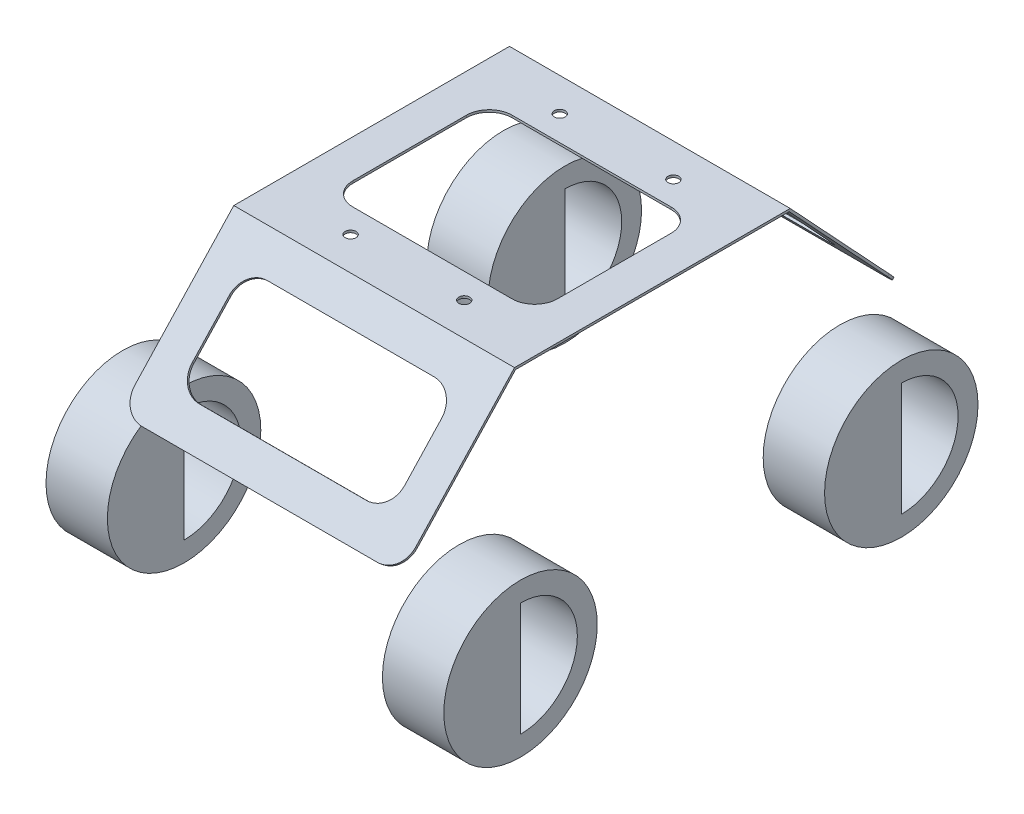
SolidWorks part; units mm, degrees
ref_plane "Plano frontal" through (0, 0, 0) normal (0, 0, 1) x (1, 0, 0)
ref_plane "Plano superior" through (0, 0, 0) normal (0, 1, 0) x (1, 0, 0)
ref_plane "Plano direito" through (0, 0, 0) normal (1, 0, 0) x (0, 0, -1)
sketch "Esboço1" plane through (0, 0, 0) normal (0, 1, 0) x (1, 0, 0)
  line L1 (-87.5, 117.5) -> (87.5, 117.5)
  line L2 (-87.5, 117.5) -> (-87.5, -117.5)
  line L3 (-87.5, -117.5) -> (87.5, -117.5)
  line L4 (87.5, 117.5) -> (87.5, -117.5)
  line L5 (-87.5, 117.5) -> (87.5, -117.5) construction
  line L6 (-87.5, -117.5) -> (87.5, 117.5) construction
  point P0 (0, 0)
  dimension "D1" = 175
  dimension "D2" = 235
extrude "Ressalto-extrusão1" add sketch "Esboço1" along normal blind 67.5
fillet "Filete1" radius 33.75 4 edges at (0, 0, -117.5) (0, 67.5, -117.5) (0, 0, 117.5) (0, 67.5, 117.5)
sketch "Esboço2" plane through (87.5, 0, 0) normal (1, 0, 0) x (0, 0, -1)
  line L0 (-83.75, 67.5) -> (83.75, 67.5)
  line L1 (83.75, 67.5) -> (83.75, 0) construction
  line L2 (83.75, 0) -> (-83.75, 0)
  line L3 (-83.75, 0) -> (-83.75, 67.5) construction
  circle A0 centre (-83.75, 33.75) radius 33.75 construction
  circle A1 centre (83.75, 33.75) radius 33.75 construction
  arc A2 (-83.75, 67.5) -> (-83.75, 0) centre (-83.75, 33.75) cw
  arc A3 (83.75, 67.5) -> (83.75, 0) centre (83.75, 33.75) ccw
extrude "Corte-extrusão1" cut sketch "Esboço2" against normal through all
sketch "Esboço3" plane through (0, 0, 0) normal (0, 0, 1) x (1, 0, 0)
  line L0 (87.5, 33.75) -> (-87.5, 33.75) construction
  line L1 (-60.5, 67.5) -> (60.5, 67.5)
  line L2 (-60.5, 67.5) -> (-60.5, 0)
  line L3 (-60.5, 0) -> (60.5, 0)
  line L4 (60.5, 67.5) -> (60.5, 0)
  line L5 (-60.5, 67.5) -> (60.5, 0) construction
  line L6 (-60.5, 0) -> (60.5, 67.5) construction
  line L7 (-87.5, 0) -> (87.5, 0) construction
  line L8 (87.5, 0) -> (87.5, 67.5) construction
  point P0 (0, 33.75)
  dimension "D1" = 27
extrude "Corte-extrusão2" cut sketch "Esboço3" against normal through all and the other way through all
ref_plane "Plano1" through (0, 70, 0) normal (0, 1, 0) x (1, 0, 0)
sketch "Esboço4" plane through (0, 70, 0) normal (0, 1, 0) x (1, 0, 0)
  line L1 (-61.75, 111) -> (61.75, 111)
  line L2 (-61.75, 111) -> (-61.75, -111)
  line L3 (-61.75, -111) -> (61.75, -111)
  line L4 (61.75, 111) -> (61.75, -111)
  line L5 (-61.75, 111) -> (61.75, -111) construction
  line L6 (-61.75, -111) -> (61.75, 111) construction
  point P0 (0, 0)
  dimension "D1" = 123.5
  dimension "D2" = 222
extrude "Ressalto-extrusão2" add sketch "Esboço4" along normal blind 54 separate body
sketch "Esboço6" plane through (61.75, 0, 0) normal (1, 0, 0) x (0, 0, -1)
  line L0 (-111, 70) -> (-111, 124)
  line L1 (-111, 124) -> (-60.6442, 124)
  line L2 (-111, 124) -> (111, 124) construction
  line L3 (-60.6442, 124) -> (-111, 70)
  line L4 (111, 124) -> (111, 70)
  line L5 (111, 70) -> (60.6442, 124)
  line L6 (60.6442, 124) -> (111, 124)
  line L7 (-109.6327, 70) -> (-60.2094, 123)
  line L8 (-111, 70) -> (111, 70) construction
  line L9 (-60.2094, 123) -> (60.2094, 123)
  line L10 (60.2094, 123) -> (109.6327, 70)
  line L11 (109.6327, 70) -> (-109.6327, 70)
  dimension "D1" = 43
  dimension "D2" = 1
  dimension "D3" = 1
  dimension "D4" = 1
extrude "Corte-extrusão3" cut sketch "Esboço6" against normal through all
sketch "Esboço7" plane through (0, 124, 0) normal (0, 1, 0) x (1, 0, 0)
  line L0 (-25, 46) -> (-25, -46) construction
  line L1 (-35, 35) -> (35, 35)
  line L2 (-45, 25) -> (-45, -25)
  line L3 (-35, -35) -> (35, -35)
  line L4 (45, 25) -> (45, -25)
  line L5 (-45, 35) -> (45, -35) construction
  line L6 (-45, -35) -> (45, 35) construction
  line L7 (-25, 46) -> (25, 46) construction
  line L8 (-25, -46) -> (25, -46) construction
  line L9 (25, 46) -> (25, -46) construction
  line L10 (-25, -46) -> (25, 46) construction
  line L11 (-25, 46) -> (25, -46) construction
  arc A0 (35, -35) -> (45, -25) centre (35, -25) ccw
  arc A1 (-45, -25) -> (-35, -35) centre (-35, -25) ccw
  arc A2 (35, 35) -> (45, 25) centre (35, 25) cw
  arc A3 (-35, 35) -> (-45, 25) centre (-35, 25) ccw
  circle A4 centre (-25, -46) radius 2.4
  circle A5 centre (25, -46) radius 2.4
  circle A6 centre (-25, 46) radius 2.4
  circle A7 centre (25, 46) radius 2.4
  point P0 (0, 0)
  dimension "D3" = 10
  dimension "D6" = 4.8
  dimension "D1" = 70
  dimension "D2" = 90
  dimension "D4" = 92
  dimension "D5" = 50
extrude "Corte-extrusão4" cut sketch "Esboço7" against normal through all
sketch "Esboço8" plane through (0, 87.9233, -94.2862) normal (0, 0.682, -0.7314) x (-1, 0, 0)
  line L0 (61.75, 49.3286) -> (61.75, -24.5071) construction
  line L1 (-36.75, 34.3286) -> (36.75, 34.3286)
  line L2 (-46.75, 24.3286) -> (-46.75, 0.4929)
  line L3 (-36.75, -9.5071) -> (36.75, -9.5071)
  line L4 (46.75, 24.3286) -> (46.75, 0.4929)
  line L5 (-46.75, 34.3286) -> (46.75, -9.5071) construction
  line L6 (-46.75, -9.5071) -> (46.75, 34.3286) construction
  line L7 (-61.75, 49.3286) -> (-61.75, -24.5071) construction
  line L8 (61.75, 49.3286) -> (-61.75, 49.3286) construction
  line L9 (-61.75, -24.5071) -> (61.75, -24.5071) construction
  line L13 (0, 12.4108) -> (0, -24.5071) construction
  arc A0 (36.75, -9.5071) -> (46.75, 0.4929) centre (36.75, 0.4929) ccw
  arc A1 (-46.75, 0.4929) -> (-36.75, -9.5071) centre (-36.75, 0.4929) ccw
  arc A2 (36.75, 34.3286) -> (46.75, 24.3286) centre (36.75, 24.3286) cw
  arc A3 (-36.75, 34.3286) -> (-46.75, 24.3286) centre (-36.75, 24.3286) ccw
  arc A4 (51.75, -24.5071) -> (61.75, -14.5071) centre (51.75, -14.5071) ccw
  arc A5 (-61.75, -14.5071) -> (-51.75, -24.5071) centre (-51.75, -14.5071) ccw
  point P0 (0, 12.4108)
  point P36 (61.75, -24.5071)
  point P39 (-61.75, -24.5071)
  line M2 (-61.75, 49.3286) -> (-61.75, -24.5071)
  line M3 (-61.75, -24.5071) -> (61.75, -24.5071)
  line M4 (61.75, -24.5071) -> (61.75, 49.3286)
  dimension "D5" = 10
  dimension "D6" = 10
  dimension "D1" = 15
  dimension "D2" = 15
  dimension "D3" = 15
  dimension "D4" = 15
extrude "Corte-extrusão5" cut sketch "Esboço8" against normal blind 10 contours L1 A3 L2 A1 L3 A0 L4 A2 | A5 M2 M3 | A4 M3 M4 region at (0, 97, -85.8221) region at (59.5163, 71.6336, -109.4766) region at (-59.5163, 71.6336, -109.4766)
mirror "Espelhar1" about plane through (0, 0, 0) normal (0, 0, 1) of "Corte-extrusão5"
sketch "Esboço9" plane through (87.5, 0, 0) normal (1, 0, 0) x (0, 0, -1)
  line L0 (-83.75, 58.75) -> (-83.75, 8.75)
  line L1 (83.75, 58.75) -> (83.75, 8.75)
  arc A0 (-83.75, 8.75) -> (-83.75, 58.75) centre (-83.75, 33.75) ccw
  arc A1 (83.75, 8.75) -> (83.75, 58.75) centre (83.75, 33.75) ccw
  point P7 (83.75, 33.75)
  dimension "D1" = 25
extrude "Corte-extrusão6" cut sketch "Esboço9" against normal through all
